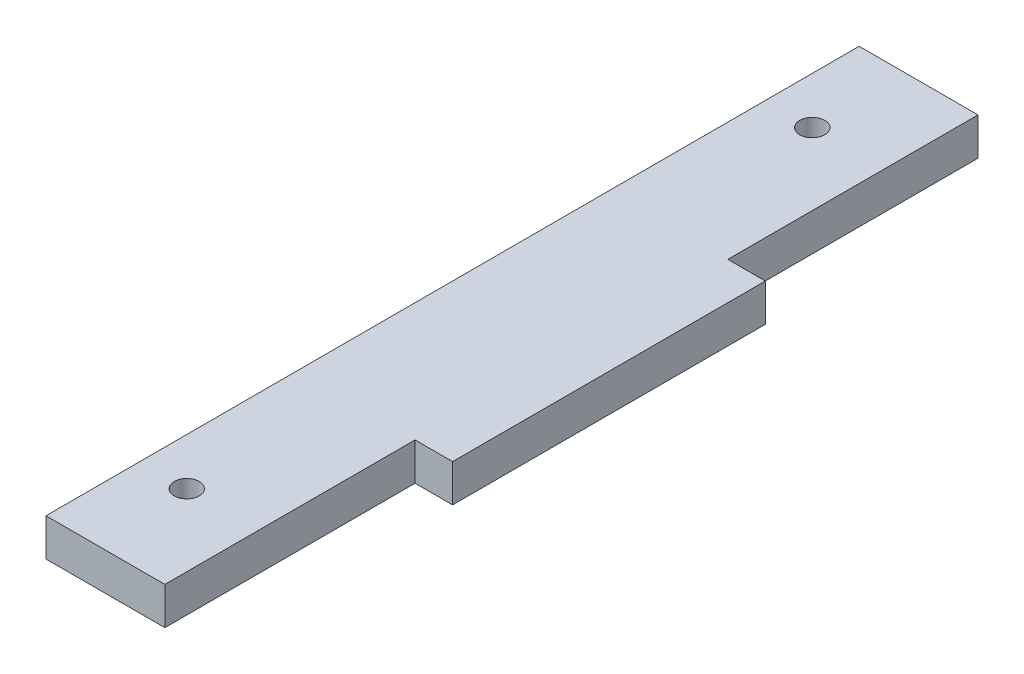
SolidWorks part; units mm, degrees
ref_plane "前视" through (0, 0, 0) normal (0, 0, 1) x (1, 0, 0)
ref_plane "上视" through (0, 0, 0) normal (0, 1, 0) x (1, 0, 0)
ref_plane "右视" through (0, 0, 0) normal (1, 0, 0) x (0, 0, -1)
sketch "Sketch1" plane through (0, 0, 0) normal (0, 1, 0) x (1, 0, 0)
  line L0 (4.3716, 58.7932) -> (4.3716, 18.7932)
  line L1 (-14.6284, 58.7932) -> (10.3716, 58.7932)
  line L2 (-14.6284, 58.7932) -> (-14.6284, -71.2068)
  line L3 (-14.6284, -71.2068) -> (10.3716, -71.2068)
  line L4 (10.3716, 58.7932) -> (10.3716, -71.2068)
  line L5 (4.3716, 18.7932) -> (10.3716, 18.7932)
  line L6 (4.3716, -31.2068) -> (4.3716, -71.2068)
  line L7 (4.3716, -31.2068) -> (10.3716, -31.2068)
  dimension "D1" = 130
  dimension "D2" = 25
  dimension "D3" = 40
  dimension "D4" = 40
  dimension "D5" = 6
extrude "Boss-Extrude1" add sketch "Sketch1" along normal blind 6 contours L6 L7 L4 L5 L0 L1 L2 L3 region at (-3.7746, 0, 6.2068)
sketch "Sketch2" plane through (0, 6, 0) normal (0, 1, 0) x (1, 0, 0)
  line L0 (-14.6284, 58.7932) -> (-14.6284, -71.2068) construction
  line L1 (-14.6284, -71.2068) -> (4.3716, -71.2068) construction
  line L2 (-14.6284, 58.7932) -> (4.3716, 58.7932) construction
  circle A0 centre (-7.1284, -56.2068) radius 2
  circle A1 centre (-7.1284, 43.7932) radius 2
  dimension "D1" = 7.5
  dimension "D2" = 7.5
  dimension "D3" = 15
  dimension "D4" = 15
extrude "Cut-Extrude1" cut sketch "Sketch2" against normal through all
